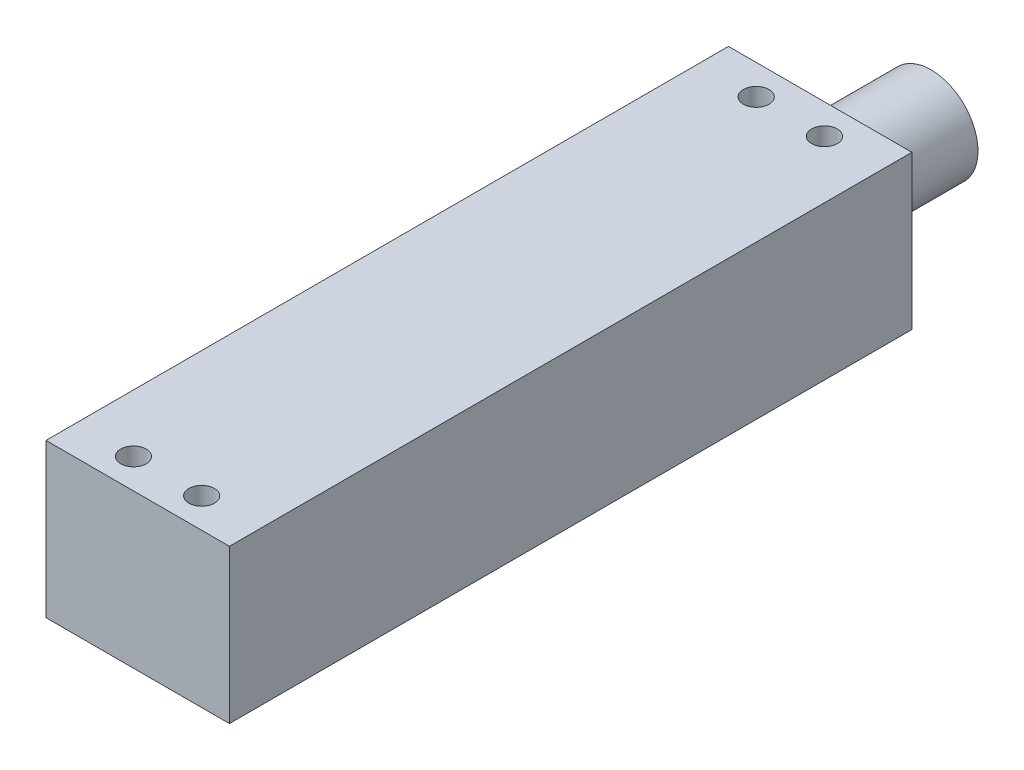
SolidWorks part; units mm, degrees
material "Chrome Stainless Steel"
ref_plane "Front Plane" through (0, 0, 0) normal (0, 0, 1) x (1, 0, 0)
ref_plane "Top Plane" through (0, 0, 0) normal (0, 1, 0) x (1, 0, 0)
ref_plane "Right Plane" through (0, 0, 0) normal (1, 0, 0) x (0, 0, -1)
ref_plane "Plane9" through (0, 10, 0) normal (0, 1, 0) x (1, 0, 0)
sketch "Sketch22" plane through (0, 0, 0) normal (0, 1, 0) x (1, 0, 0)
  line L5 (5.5, -119.3995) -> (-16, -199.3995) construction
  line L6 (5.5, -119.3995) -> (-16, -119.3995)
  line L7 (5.5, -119.3995) -> (5.5, -199.3995)
  line L8 (5.5, -199.3995) -> (-16, -199.3995)
  line L9 (-16, -119.3995) -> (-16, -199.3995)
  line L10 (-5.25, -199.3995) -> (-5.25, -119.3995) construction
  line L11 (5.5, -159.3995) -> (-16, -159.3995) construction
  point P4 (-5.25, -159.3995)
  point P6 (0, 0)
  dimension "D3" = 21.5
  dimension "D4" = 80
extrude "Boss-Extrude6" add sketch "Sketch22" along normal blind 18 from surface separate body starting at plane "Plane9"
sketch "Sketch23" plane through (0, 28, 0) normal (0, 1, 0) x (1, 0, 0)
  line L0 (-1.25, -195.8995) -> (-9.25, -195.8995) construction
  line L1 (-5.25, -122.8995) -> (-5.25, -195.8995) construction
  line L2 (5.5, -159.3995) -> (-16, -159.3995) construction
  line L3 (-1.25, -122.8995) -> (-9.25, -122.8995) construction
  line L4 (-16, -199.3995) -> (-16, -119.3995) construction
  circle A0 centre (-9.25, -122.8995) radius 1.5
  circle A1 centre (-1.25, -122.8995) radius 1.5
  circle A2 centre (-1.25, -195.8995) radius 1.5
  circle A3 centre (-9.25, -195.8995) radius 1.5
  point P5 (-5.25, -195.8995)
  point P9 (-5.25, -122.8995)
  point P17 (-5.25, -159.3995)
  point P19 (-5.25, -159.3995)
  dimension "D2" = 3
  dimension "D3" = 3
  dimension "D1" = 8
  dimension "D4" = 73
extrude "Cut-Extrude9" cut sketch "Sketch23" against normal blind 4
sketch "Sketch24" plane through (0, 0, 119.3995) normal (0, 0, -1) x (-1, 0, 0)
  circle A2 centre (5.25, 19) radius 4
  circle A3 centre (5.25, 19) radius 5.5
  dimension "D1" = 11
extrude "Boss-Extrude7" add sketch "Sketch24" along normal blind 13
